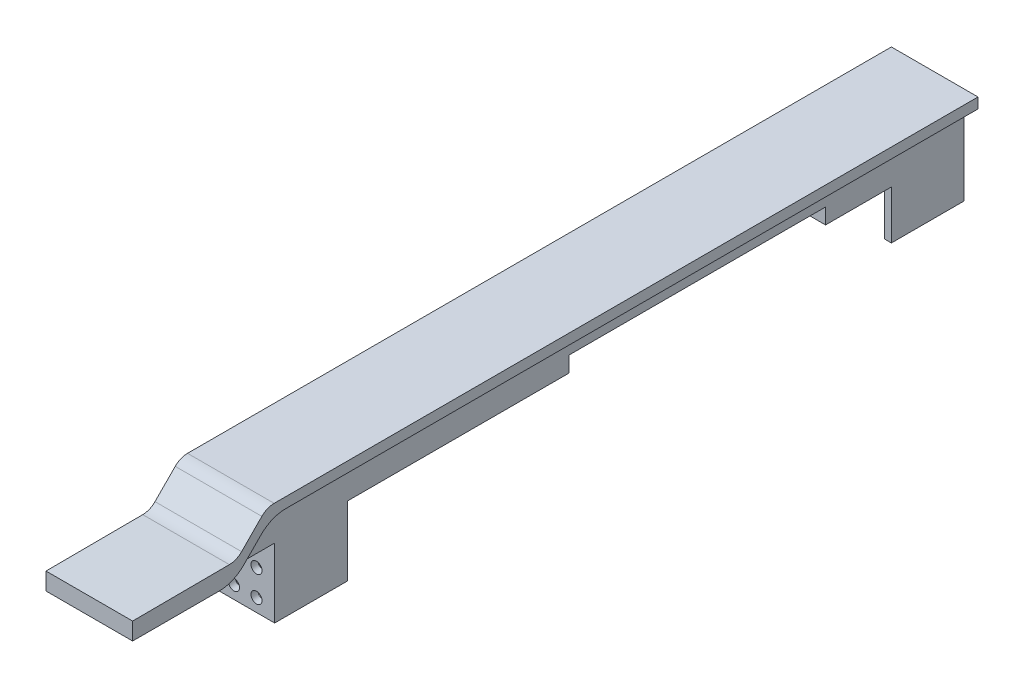
SolidWorks part; units mm, degrees
ref_plane "Front Plane" through (0, 0, 0) normal (0, 0, 1) x (1, 0, 0)
ref_plane "Top Plane" through (0, 0, 0) normal (0, 1, 0) x (1, 0, 0)
ref_plane "Right Plane" through (0, 0, 0) normal (1, 0, 0) x (0, 0, -1)
sketch "Sketch1" plane through (0, 0, 0) normal (1, 0, 0) x (0, 0, -1)
  line L0 (0, 0) -> (-130, 0)
  line L1 (0, 0) -> (74, 0) construction
  line L2 (0, 0) -> (0, 4.5)
  line L3 (0, 4.5) -> (74, 4.5)
  line L4 (74, 4.5) -> (74, 0)
  line L5 (74, 0) -> (114, 0)
  line L6 (-130, 0) -> (-130, 5)
  line L7 (-130, 5) -> (-100.0004, 5.1483)
  line L8 (-100.0004, 5.1483) -> (-91.2357, 14)
  line L11 (114, 14) -> (-91.2357, 14)
  line L12 (114, 0) -> (114, 14)
  dimension "D1" = 130
  dimension "D2" = 74
  dimension "D3" = 4.5
  dimension "D4" = 40
  dimension "D5" = 30
  dimension "D6" = 5
  dimension "D7" = 135
  dimension "D8" = 9.5
extrude "Boss-Extrude1" add sketch "Sketch1" along normal blind 25
sketch "Sketch4" plane through (25, 0, 0) normal (1, 0, 0) x (0, 0, -1)
  line L11 (-130, 0) -> (0, 0) construction
  line L12 (-130, 0) -> (0, 0) construction
  line L13 (-100.8762, 0) -> (0, 0)
  line L14 (0, 0) -> (111, 0)
  line L15 (74, 0) -> (114, 0) construction
  line L16 (111, 0) -> (111, 3)
  line L22 (-3, 3) -> (-3, 7.5)
  line L23 (-3, 7.5) -> (77, 7.5)
  line L24 (77, 7.5) -> (77, 3)
  line L25 (77, 3) -> (111, 3)
  line L26 (111, 3) -> (111, 11)
  line L28 (111, 11) -> (-89.9844, 11)
  line L29 (-89.9844, 11) -> (-97.9057, 3)
  line L30 (-97.9057, 3) -> (-3, 3)
  line L35 (111, 3) -> (111, 11)
  line L37 (111, 11) -> (-89.9844, 11)
  line L38 (-89.9844, 11) -> (-100.8762, 0)
  dimension "D1" = 3
ref_plane "Plane1" through (12.5, 0, 0) normal (1, 0, 0) x (0, 0, -1)
sketch "Sketch5" plane through (12.5, 0, 0) normal (1, 0, 0) x (0, 0, -1)
  line L0 (-117.866, 5.06) -> (-112.2372, 10.7447)
  line L1 (-100.0004, 5.1483) -> (-130, 5) construction
  line L2 (-91.2357, 14) -> (-100.0004, 5.1483) construction
  line L3 (-112.2372, 10.7447) -> (-81.8129, 10.7447)
  line L4 (-117.866, 5.06) -> (-95.866, 5.06)
  line L6 (-81.8129, 10.7447) -> (-95.866, 5.06)
  line L11 (-89.9844, 11) -> (-100.8762, 0) construction
  dimension "D1" = 22
  dimension "D2" = 8
sketch "Sketch6" plane through (25, 0, 0) normal (1, 0, 0) x (0, 0, -1)
  line L0 (-130, 0) -> (114, 0) construction
  line L1 (74, 0) -> (114, 0) construction
  line L2 (114, 0) -> (114, 14) construction
  line L3 (-100.8762, 0) -> (114, 0)
  line L4 (114, 0) -> (114, 11)
  line L20 (-3, 3) -> (-3, 7.5)
  line L21 (-3, 7.5) -> (77, 7.5)
  line L22 (77, 7.5) -> (77, 3)
  line L23 (77, 3) -> (111, 3)
  line L24 (111, 3) -> (111, 11)
  line L25 (111, 11) -> (-89.9844, 11)
  line L26 (-89.9844, 11) -> (-97.9057, 3)
  line L27 (-97.9057, 3) -> (-3, 3)
  line L33 (114, 11) -> (-89.9844, 11)
  line L34 (-89.9844, 11) -> (-100.8762, 0)
  dimension "D1" = 3
extrude "Cut-Extrude2" cut sketch "Sketch6" against normal blind 4
mirror "Mirror3" about plane through (12.5, 0, 0) normal (1, 0, 0) of "Cut-Extrude2"
fillet "Fillet6" radius 10 4 edges at (2, 11, 89.9844) (2, 0, 100.8762) (23, 0, 100.8762) (23, 11, 89.9844)
fillet "Fillet7" radius 5 2 edges at (12.5, 14, 91.2357) (12.5, 5.1483, 100.0004)
sketch "Sketch7" plane through (0, 0, 0) normal (0, -1, 0) x (1, 0, 0)
  line L0 (12.5, 130) -> (12.5, 85) construction
  line L1 (25, 130) -> (0, 130) construction
  line L2 (21, 85) -> (4, 85)
  line L3 (4, 105.0473) -> (4, 0) construction
  line L4 (4, 85) -> (4, 64)
  line L5 (4, 64) -> (6, 64)
  line L6 (6, 64) -> (6, 83)
  line L7 (6, 83) -> (19, 83)
  line L8 (19, 64) -> (19, 83)
  line L9 (21, 64) -> (19, 64)
  line L10 (21, 85) -> (21, 64)
  point P13 (12.5, 83)
  dimension "D1" = 45
  dimension "D2" = 21
  dimension "D3" = 2
  dimension "D4" = 2
  dimension "D5" = 6.5
extrude "Boss-Extrude2" add sketch "Sketch7" along normal blind 20
sketch "Sketch8" plane through (0, 0, 85) normal (0, 0, 1) x (1, 0, 0)
  line L0 (15.75, -8.75) -> (21, -8.75) construction
  line L1 (15.75, -8.75) -> (15.75, -5) construction
  line L2 (12.5, -20) -> (12.5, -5) construction
  line L3 (0, -12.5) -> (25, -12.5) construction
  line L4 (4, -20) -> (21, -20) construction
  line L5 (21, -20) -> (4, -20) construction
  line L6 (21, -20) -> (4, -20) construction
  line L7 (9.25, -16.25) -> (9.25, -20) construction
  line L8 (9.25, -16.25) -> (4, -16.25) construction
  line L9 (4, -20) -> (4, 0) construction
  circle A0 centre (15.75, -16.25) radius 1.6
  circle A1 centre (9.25, -16.25) radius 1.6
  circle A2 centre (9.25, -8.75) radius 1.6
  circle A3 centre (15.75, -8.75) radius 1.6
  circle A4 centre (9.25, -16.25) radius 3 construction
  dimension "D3" = 3.2
  dimension "D1" = 3.75
  dimension "D2" = 5.25
extrude "Cut-Extrude3" cut sketch "Sketch8" against normal up to surface (2 mm away) up to face at (12.5, -10, 83)
sketch "Sketch9" plane through (0, 0, 0) normal (0, -1, 0) x (1, 0, 0)
  line L0 (4, -114) -> (21, -114)
  line L1 (21, -114) -> (4, -114) construction
  line L2 (21, -114) -> (21, 85.8133) construction
  line L3 (21, -74) -> (21, -114) construction
  line L4 (21, -114) -> (21, -93)
  line L5 (21, -93) -> (19, -93)
  line L6 (19, -93) -> (19, -112)
  line L7 (19, -112) -> (6, -112)
  line L8 (12.5, -114) -> (12.5, -112) construction
  line L9 (6, -93) -> (6, -112)
  line L10 (4, -93) -> (6, -93)
  line L11 (4, -114) -> (4, -93)
  dimension "D1" = 21
  dimension "D2" = 2
  dimension "D3" = 2
extrude "Boss-Extrude3" add sketch "Sketch9" along normal blind 14 contours L9 L7 L6 L5 L4 L0 L11 L10
sketch "Sketch11" plane through (0, 0, -114) normal (0, 0, -1) x (-1, 0, 0)
  line L2 (-12.5, -14) -> (-12.5, 1) construction
  line L3 (-25, -6.5) -> (0, -6.5) construction
  line L4 (-21, -14) -> (-4, -14) construction
  line L5 (-4, -14) -> (-21, -14) construction
  line L6 (-15.75, -10.25) -> (-15.75, -14) construction
  line L7 (-15.75, -10.25) -> (-21, -10.25) construction
  line L8 (-4, -14) -> (-21, -14) construction
  line L9 (-4, -14) -> (-21, -14) construction
  line L10 (-4, -14) -> (-4, 11) construction
  circle A0 centre (-9.25, -10.25) radius 1.6
  circle A1 centre (-15.75, -10.25) radius 1.6
  circle A4 centre (-15.75, -10.25) radius 3 construction
  dimension "D3" = 3.2
  dimension "D1" = 5.25
  dimension "D2" = 3.75
extrude "Cut-Extrude4" cut sketch "Sketch11" against normal up to surface (2 mm away) up to face at (12.5, -7, -112)
